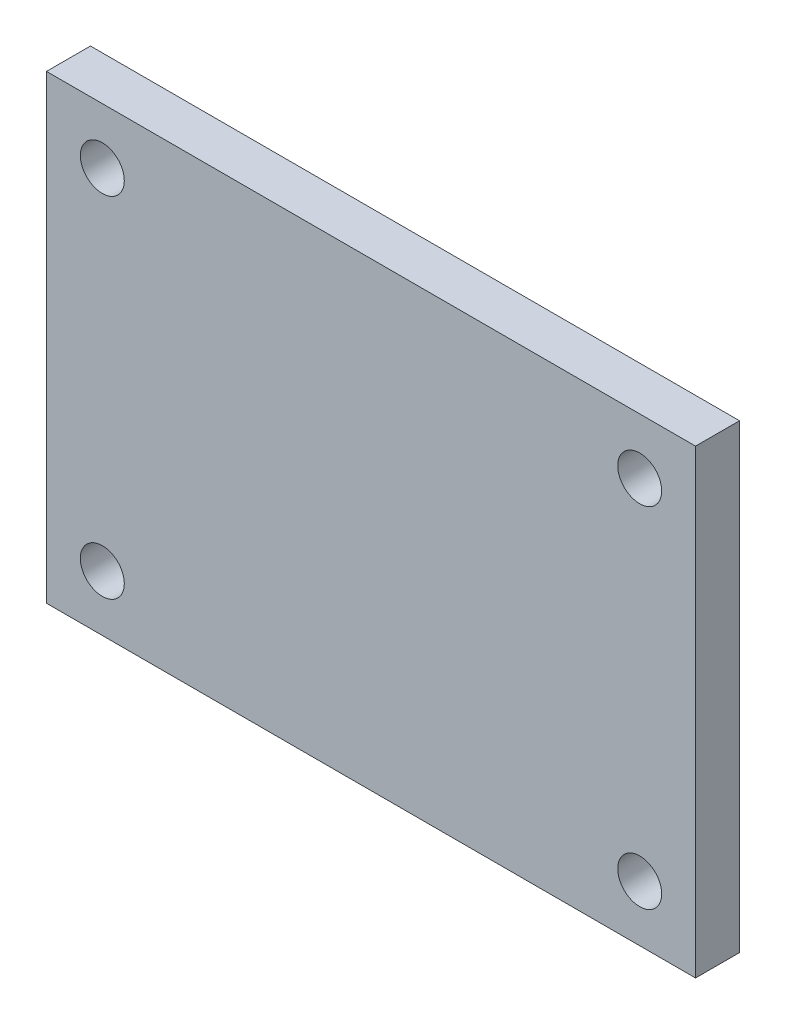
SolidWorks part; units mm, degrees
ref_plane "Plan de face" through (0, 0, 0) normal (0, 0, 1) x (1, 0, 0)
ref_plane "Plan de dessus" through (0, 0, 0) normal (0, 1, 0) x (1, 0, 0)
ref_plane "Plan de droite" through (0, 0, 0) normal (1, 0, 0) x (0, 0, -1)
sketch "Esquisse1" plane through (0, 0, 0) normal (0, 0, 1) x (1, 0, 0)
  line L1 (0, 0) -> (47.244, 0)
  line L2 (0, 0) -> (0, 33.528)
  line L3 (0, 33.528) -> (47.244, 33.528)
  line L4 (47.244, 0) -> (47.244, 33.528)
  dimension "D1" = 33.528
  dimension "D2" = 47.244
extrude "Boss.-Extru.1" add sketch "Esquisse1" along normal blind 3.2
sketch "Esquisse2" plane through (0, 0, 3.2) normal (0, 0, 1) x (1, 0, 0)
  line L0 (47.244, 33.528) -> (0, 33.528) construction
  line L2 (0, 33.528) -> (0, 0) construction
  line L3 (47.244, 0) -> (47.244, 33.528) construction
  line L4 (0, 0) -> (47.244, 0) construction
  circle A0 centre (4.064, 29.464) radius 1.6
  circle A1 centre (43.18, 29.464) radius 1.6
  circle A2 centre (43.18, 4.064) radius 1.6
  circle A3 centre (4.064, 4.064) radius 1.6
  point P12 (0, 31.3488)
  point P15 (21.9883, 40.1813)
  dimension "D3" = 3.2
  dimension "D6" = 3.2
  dimension "D9" = 3.2
  dimension "D12" = 3.2
  dimension "D1" = 4.064
  dimension "D2" = 4.064
  dimension "D4" = 4.064
  dimension "D5" = 4.064
  dimension "D7" = 4.064
  dimension "D8" = 4.064
  dimension "D10" = 4.064
  dimension "D11" = 4.064
extrude "Enlèv. mat.-Extru.1" cut sketch "Esquisse2" against normal up to surface (3.2 mm away) up to face at (23.622, 16.764, 0)
sketch "Esquisse3" plane through (0, 0, 3.2) normal (0, 0, 1) x (1, 0, 0)
  text T0 "<b>Interface with probes</b>"
